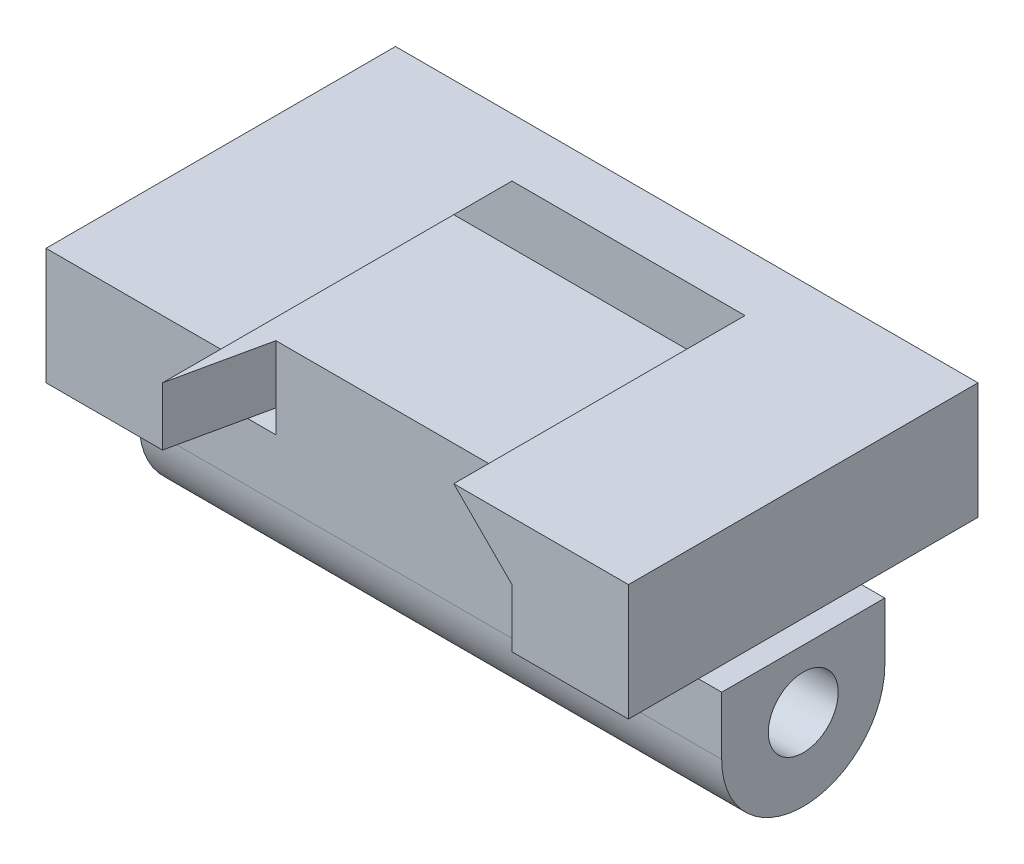
SolidWorks part; units mm, degrees
material "ABS"
ref_plane "Front Plane" through (0, 0, 0) normal (0, 0, 1) x (1, 0, 0)
ref_plane "Top Plane" through (0, 0, 0) normal (0, 1, 0) x (1, 0, 0)
ref_plane "Right Plane" through (0, 0, 0) normal (1, 0, 0) x (0, 0, -1)
sketch "Sketch1" plane through (0, 0, 0) normal (0, 1, 0) x (1, 0, 0)
  line L0 (0, 0) -> (0, 6.9526) construction
  line L1 (-25, 15) -> (-15, 15)
  line L2 (-25, 15) -> (-25, -15)
  line L3 (-25, -15) -> (-15, -15)
  line L4 (-15, 15) -> (-15, -15)
  line L5 (-25, 15) -> (-15, -15) construction
  line L6 (-25, -15) -> (-15, 15) construction
  line L7 (25, -15) -> (15, 15) construction
  line L8 (25, 15) -> (15, -15) construction
  line L9 (15, 15) -> (15, -15)
  line L10 (25, -15) -> (15, -15)
  line L11 (25, 15) -> (25, -15)
  line L12 (25, 15) -> (15, 15)
  line L13 (-15, 15) -> (15, 15)
  line L22 (-15, -15) -> (15, -15)
  line L23 (-15, -15) -> (-13.2665, -7)
  line L24 (-13.2665, -7) -> (13.2665, -7)
  line L25 (15, -15) -> (13.2665, -7)
  line L26 (-13.2665, 7) -> (13.2665, 7)
  circle A0 centre (0, 0) radius 15
  point P0 (-20, 0)
  point P12 (20, 0)
  point P18 (0, -7)
  dimension "D1" = 30
  dimension "D2" = 30
  dimension "D3" = 10
extrude "Boss-Extrude1" add sketch "Sketch1" along normal blind 5 contours L4 L1 L2 L3 | L11 L12 L9 L10 | L24 A0 L26 | L26 A0 | A0 L13 L4 | A0 L4 L23 | A0 L9 L13 | A0 L25 L9 region at (-20, 0, 0) region at (-11.6495, 0, -11.6495) region at (-14.4452, 0, 8.0723) region at (0, 0, 0) region at (11.6495, 0, -11.6495) region at (0, 0, -10.2867) region at (20, 0, 0) region at (14.4452, 0, 8.0723)
sketch "Sketch4" plane through (0, 0, 0) normal (0, -1, 0) x (1, 0, 0)
  line L0 (0, 0) -> (0, 7) construction
  line L1 (0, 0) -> (4.9545, 0) construction
  line L2 (-13.2665, 7) -> (13.2665, 7)
  line L3 (-13.2665, -7) -> (13.2665, -7)
  circle A0 centre (0, 0) radius 15
  point P8 (0, 7)
extrude "Boss-Extrude2" add sketch "Sketch4" along normal blind 2 contours L3 A0 L2 region at (0, 0, 0)
sketch "Sketch10" plane through (0, 0, 15) normal (0, 0, 1) x (1, 0, 0)
  line L0 (-15, 5) -> (-10, 10)
  line L1 (-25, 5) -> (-15, 5)
  line L2 (-25, 5) -> (-25, 10)
  line L3 (-25, 10) -> (-15, 10)
  line L4 (-15, 5) -> (-15, 10)
  line L5 (-10, 10) -> (-15, 10)
  line L8 (10, 10) -> (15, 10)
  line L9 (15, 5) -> (15, 10)
  line L10 (25, 10) -> (15, 10)
  line L11 (25, 5) -> (25, 10)
  line L12 (25, 5) -> (15, 5)
  line L13 (15, 5) -> (10, 10)
  point P5 (0, 0)
  line M6 (25, 5) -> (15, 5)
extrude "Boss-Extrude7" add sketch "Sketch10" against normal blind 30 contours L4 L3 L2 M6 | L0 L5 L4 | L13 L9 L8 | L11 L10 L9 M6 region at (-13.3333, 8.3333, 15) region at (-20, 7.5, 15) region at (13.3333, 8.3333, 15) region at (20, 7.5, 15)
sketch "Sketch11" plane through (25, 0, 0) normal (1, 0, 0) x (0, 0, -1)
  line L0 (0, 0) -> (0, -7) construction
  line L1 (15, 0) -> (-15, 0) construction
  line L2 (-7, -7) -> (-7, -2)
  line L3 (-7, -2) -> (7, -2)
  line L4 (7, -2) -> (7, -7)
  circle A0 centre (0, -7) radius 3
  arc A1 (-7, -7) -> (7, -7) centre (0, -7) ccw
extrude "Boss-Extrude8" add sketch "Sketch11" against normal blind 50
sketch "Sketch12" plane through (0, 0, -15) normal (0, 0, -1) x (-1, 0, 0)
  line L0 (-15, 5) -> (15, 5)
  line L1 (15, 5) -> (10, 10)
  line L2 (10, 10) -> (-10, 10)
  line L3 (-10, 10) -> (-15, 5)
extrude "Boss-Extrude9" add sketch "Sketch12" against normal blind 5
